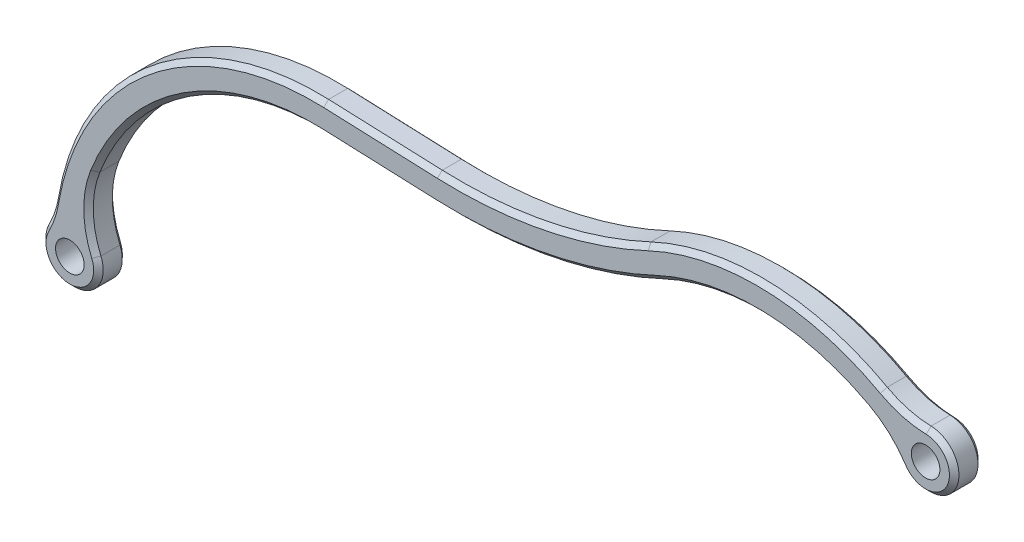
SolidWorks part; units mm, degrees
ref_plane "Спереди" through (0, 0, 0) normal (0, 0, 1) x (1, 0, 0)
ref_plane "Сверху" through (0, 0, 0) normal (0, 1, 0) x (1, 0, 0)
ref_plane "Справа" through (0, 0, 0) normal (1, 0, 0) x (0, 0, -1)
other "Configuration Table"
sketch "Sketch1" plane through (0, 0, 0) normal (0, 0, 1) x (1, 0, 0)
  line L1 (-80.1701, 9.5124) -> (-68.2504, 9.0423)
  line L2 (-73.3782, 12.4829) -> (-82.8708, 12.8573) construction
  line L3 (-80.2292, 8.0135) -> (-68.3095, 7.5434)
  line L4 (-80.111, 11.0112) -> (-68.1913, 10.5411)
  circle A0 centre (-17, 9.9282) radius 3
  circle A1 centre (-17, 9.9282) radius 1.5
  arc A2 (-107.2137, -14.3694) -> (-80.1701, 9.5124) centre (-81.1989, -16.5755) cw construction
  circle A3 centre (-106.7589, -16.339) radius 3
  circle A4 centre (-106.7589, -16.339) radius 1.5
  arc A6 (-107.2027, -14.2426) -> (-80.1701, 9.5124) centre (-81.1989, -16.5755) cw
  arc A7 (-68.2504, 9.0423) -> (-45.6614, 13.6144) centre (-66.3331, 57.6572) ccw
  arc A8 (-45.6614, 13.6144) -> (-18.7607, 10.5516) centre (-34.6965, -9.7473) cw
  arc A9 (-105.7191, -14.4961) -> (-80.2292, 8.0135) centre (-81.1989, -16.5755) cw
  arc A10 (-68.3095, 7.5434) -> (-45.0241, 12.2565) centre (-66.3331, 57.6572) ccw
  arc A11 (-45.0241, 12.2565) -> (-19.8142, 9.471) centre (-34.6965, -9.7473) cw
  arc A12 (-108.7084, -14.2426) -> (-80.111, 11.0112) centre (-81.1989, -16.5755) cw
  arc A13 (-68.1913, 10.5411) -> (-46.2987, 14.9723) centre (-66.3331, 57.6572) ccw
  arc A14 (-46.2987, 14.9723) -> (-17.9774, 11.843) centre (-34.6965, -9.7473) cw
  arc A15 (-45.6614, 13.6144) -> (-18.8958, 10.657) centre (-34.6965, -9.7473) cw construction
  point P15 (-107.2027, -14.2426)
  dimension "D1" = 6
  dimension "D2" = 3
  dimension "D3" = 6
  dimension "D4" = 3
  dimension "D5" = 1.5
  dimension "D6" = 1.5
extrude "Boss-Extrude1" add sketch "Sketch1" along normal blind 3 contours A3 A4 | A14 A13 L4 A12 A3 A6 L1 A7 A8 A0 | A10 A11 A0 A8 A7 L1 A6 A3 A9 L3 | A0 A1 region at (-98.7141, 4.0537, 0) region at (-74.2466, 8.3551, 0) region at (-106.3637, -13.4507, 0) region at (-19.2108, 11.8284, 0)
fillet "Fillet1" radius 10 4 edges at (-18.7116, 12.392, 1.5) (-19.982, 9.5998, 1.5) (-108.6908, -14.0438, 1.5) (-105.622, -13.5627, 1.5)
chamfer "Chamfer1" distance 0.5 angle 45 28 edges at (-34.0123, 14.55, 0) (-56.3837, 8.5013, 0) (-21.1211, 10.1944, 0) (-74.2693, 7.7785, 0) (-14.3806, 8.4658, 0) (-94.6614, 4.0236, 0) (-19.2954, 13.2708, 0) (-104.7981, -11.3889, 0) (-33.8096, 17.5452, 0) (-106.8761, -19.3367, 0) (-56.9788, 11.4416, 0) (-108.8042, -13.5081, 0) (-74.1511, 10.7761, 0) (-98.6059, 4.8536, 0) (-34.0123, 14.55, 3) (-56.3837, 8.5013, 3) (-21.1211, 10.1944, 3) (-74.2693, 7.7785, 3) (-14.3806, 8.4658, 3) (-94.6614, 4.0236, 3) (-19.2954, 13.2708, 3) (-104.7981, -11.3889, 3) (-33.8096, 17.5452, 3) (-106.8761, -19.3367, 3) (-56.9788, 11.4416, 3) (-108.8042, -13.5081, 3) (-74.1511, 10.7761, 3) (-98.6059, 4.8536, 3)
